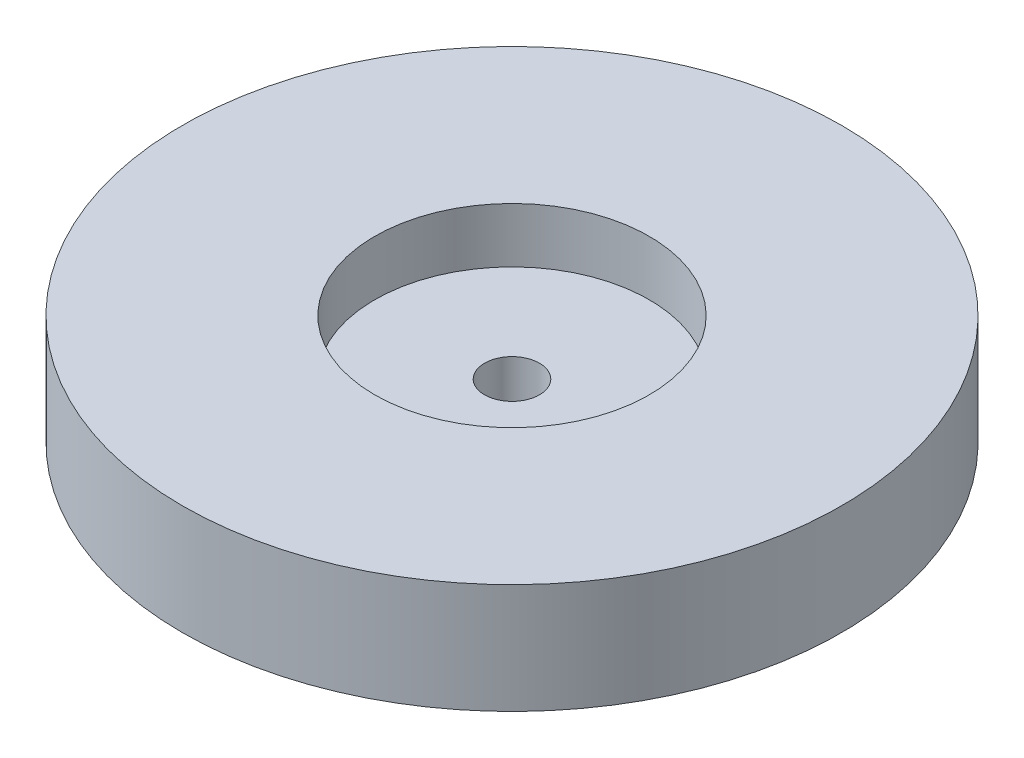
SolidWorks part; units mm, degrees
ref_plane "Front Plane" through (0, 0, 0) normal (0, 0, 1) x (1, 0, 0)
ref_plane "Top Plane" through (0, 0, 0) normal (0, 1, 0) x (1, 0, 0)
ref_plane "Right Plane" through (0, 0, 0) normal (1, 0, 0) x (0, 0, -1)
sketch "Sketch1" plane through (0, 0, 0) normal (0, 1, 0) x (1, 0, 0)
  circle A0 centre (0, 0) radius 30
  circle A1 centre (0, 0) radius 2.5
  circle A2 centre (0, 0) radius 12.5
  dimension "D1" = 60
  dimension "D2" = 5
  dimension "D3" = 25
extrude "Boss-Extrude1" add sketch "Sketch1" along normal blind 10 contours A0 A2 region at (-29.1515, 0, 0)
extrude "Boss-Extrude2" add sketch "Sketch1<3>" along normal blind 5 contours A2 A1 region at (-12.1464, 0, 0)
sketch "Sketch1<3>" plane through (0, 0, 0) normal (0, 1, 0) x (1, 0, 0) same geometry as "Sketch1"
